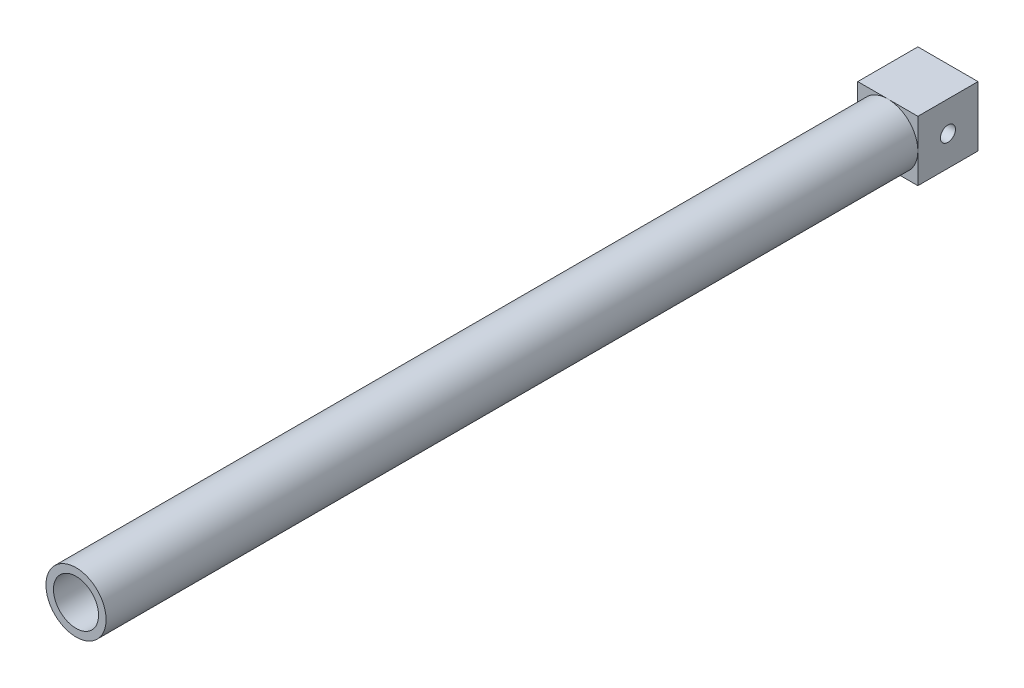
SolidWorks part; units mm, degrees
ref_plane "Plano frontal" through (0, 0, 0) normal (0, 0, 1) x (1, 0, 0)
ref_plane "Plano superior" through (0, 0, 0) normal (0, 1, 0) x (1, 0, 0)
ref_plane "Plano direito" through (0, 0, 0) normal (1, 0, 0) x (0, 0, -1)
sketch "Esboço1" plane through (0, 0, 0) normal (0, 0, 1) x (1, 0, 0)
  circle A0 centre (0, 0) radius 10
extrude "Ressalto-extrusão1" add sketch "Esboço1" along normal blind 280 and the other way blind 10
sketch "Esboço2" plane through (0, 0, 0) normal (0, 0, 1) x (1, 0, 0)
  circle A0 centre (0, 0) radius 7.5
extrude "Corte-extrusão1" cut sketch "Esboço2" along normal blind 280
sketch "Esboço3" plane through (0, 0, 0) normal (1, 0, 0) x (0, 0, -1)
  circle A0 centre (0, 0) radius 2.5
sketch "Esboço4" plane through (0, 0, 0) normal (0, 0, 1) x (1, 0, 0)
  line L1 (10, -10) -> (-10, -10)
  line L2 (10, -10) -> (10, 10)
  line L3 (10, 10) -> (-10, 10)
  line L4 (-10, -10) -> (-10, 10)
  line L5 (10, -10) -> (-10, 10) construction
  line L6 (10, 10) -> (-10, -10) construction
  point P0 (0, 0)
extrude "Ressalto-extrusão2" add sketch "Esboço4" along normal blind 10 and the other way blind 10
extrude "Corte-extrusão2" cut sketch "Esboço3" against normal blind 10 and the other way blind 10
